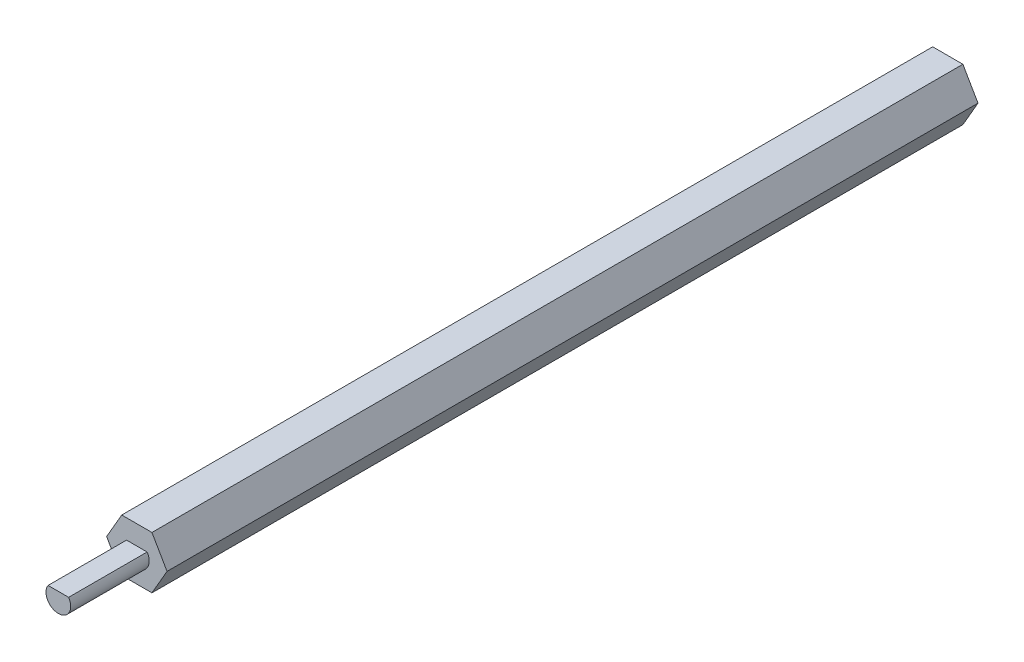
SolidWorks part; units mm, degrees
ref_plane "Front Plane" through (0, 0, 0) normal (0, 0, 1) x (1, 0, 0)
ref_plane "Top Plane" through (0, 0, 0) normal (0, 1, 0) x (1, 0, 0)
ref_plane "Right Plane" through (0, 0, 0) normal (1, 0, 0) x (0, 0, -1)
sketch "Sketch1" plane through (0, 0, 0) normal (0, 0, 1) x (1, 0, 0)
  line L1 (3.6662, 6.35) -> (-3.6662, 6.35)
  line L2 (-3.6662, 6.35) -> (-7.3323, 0)
  line L3 (-7.3323, 0) -> (-3.6662, -6.35)
  line L4 (-3.6662, -6.35) -> (3.6662, -6.35)
  line L5 (3.6662, -6.35) -> (7.3323, 0)
  line L6 (7.3323, 0) -> (3.6662, 6.35)
  circle A0 centre (0, 0) radius 6.35 construction
  dimension "D1" = 12.7
extrude "Boss-Extrude1" add sketch "Sketch1" along normal mid plane 215.9
ref_axis "Axis1" through (0, 0, -83.82) along (0, 0, 1)
sketch "Sketch2" plane through (0, 0, 107.95) normal (0, 0, 1) x (1, 0, 0)
  line L0 (-7.3323, 0) -> (-3.6662, -6.35)
  line L1 (-7.3323, 0) -> (-3.6662, -6.35) construction
  line L2 (-3.6662, -6.35) -> (3.6662, -6.35) construction
  line L3 (-3.6662, -6.35) -> (3.6662, -6.35)
  line L4 (3.6662, -6.35) -> (7.3323, 0)
  line L5 (7.3323, 0) -> (3.6662, 6.35)
  line L6 (3.6662, 6.35) -> (-3.6662, 6.35)
  line L7 (-3.6662, 6.35) -> (-7.3323, 0)
  line L8 (-2.5, 1.6583) -> (2.5, 1.6583)
  circle A0 centre (0, 0) radius 3
  line M3 (7.3323, 0) -> (3.6662, 6.35)
  line M4 (3.6662, 6.35) -> (-3.6662, 6.35)
  line M5 (-3.6662, 6.35) -> (-7.3323, 0)
  line M6 (-7.3323, 0) -> (-3.6662, -6.35)
  line M7 (-3.6662, -6.35) -> (3.6662, -6.35)
  line M8 (3.6662, -6.35) -> (7.3323, 0)
  dimension "D1" = 6
  dimension "D2" = 5
extrude "Cut-Extrude1" cut sketch "Sketch2" against normal blind 19.05 contours L8 A0 | A0 M8 M3 M4 M5 M6 M7 region at (-5.3313, 3.078, 107.95) region at (0, 2.2068, 107.95)
